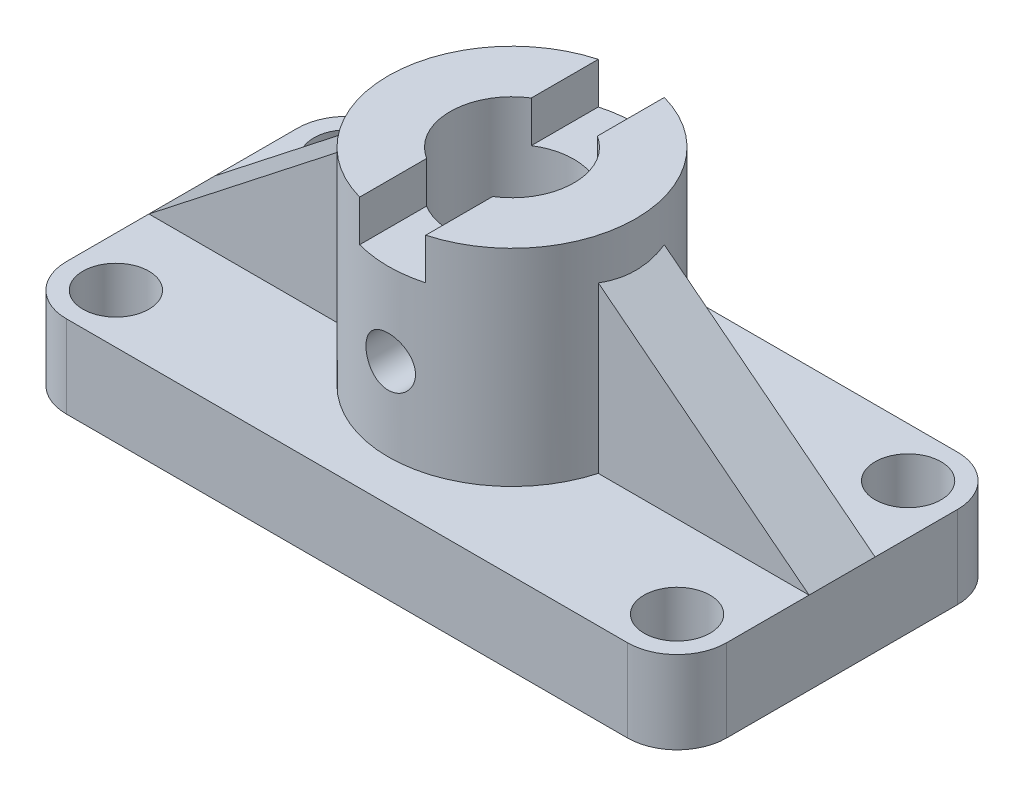
SolidWorks part; units mm, degrees
ref_plane "前视基准面" through (0, 0, 0) normal (0, 0, 1) x (1, 0, 0)
ref_plane "上视基准面" through (0, 0, 0) normal (0, 1, 0) x (1, 0, 0)
ref_plane "右视基准面" through (0, 0, 0) normal (1, 0, 0) x (0, 0, -1)
other "Configuration Table"
sketch "草图2" plane through (0, 0, 0) normal (0, 1, 0) x (1, 0, 0)
  line L0 (-1000, 0) -> (49000, 0) construction
  line L1 (34, -20) -> (-34, -20)
  line L2 (40, -14) -> (40, 14)
  line L3 (34, 20) -> (-34, 20)
  line L4 (-40, -14) -> (-40, 14)
  line L5 (40, -20) -> (-40, 20) construction
  line L6 (40, 20) -> (-40, -20) construction
  line L7 (0, -1000) -> (0, 49000) construction
  line L8 (40, -4) -> (14.4568, -4)
  line L9 (-40, 4) -> (-14.4568, 4)
  line L10 (-40, 4) -> (-40, -4)
  line L11 (-40, -4) -> (-14.4568, -4)
  line L13 (40, 4) -> (14.4568, 4)
  arc A0 (-34, -20) -> (-40, -14) centre (-34, -14) cw
  arc A1 (34, -20) -> (40, -14) centre (34, -14) ccw
  arc A2 (34, 20) -> (40, 14) centre (34, 14) cw
  arc A3 (-34, 20) -> (-40, 14) centre (-34, 14) ccw
  circle A4 centre (34, 14) radius 4
  circle A5 centre (34, -14) radius 4
  circle A6 centre (-34, -14) radius 4
  circle A7 centre (-34, 14) radius 4
  circle A8 centre (0, 0) radius 7.5
  circle A9 centre (0, 0) radius 15
  point P0 (0, 0)
  dimension "D1" = 6
  dimension "D4" = 8
  dimension "D5" = 15
  dimension "D6" = 30
  dimension "D2" = 80
  dimension "D3" = 40
  dimension "D7" = 8
extrude "凸台-拉伸1" add sketch "草图2" along normal blind 10 contours A9 L13 L2 A2 L3 A3 L4 L9 A7 A4 | A9 L8 L2 L13 | A9 L11 L4 A0 L1 A1 L2 L8 A5 A6 | A9 L9 L4 L11 region at (0, 0, 19.1842) region at (27.4096, 0, 0) region at (-27.4096, 0, 0) region at (27.2284, 0, -4.8158)
extrude "凸台-拉伸2" add sketch "草图2<3>" along normal blind 35 contours A9 A8 region at (0, 0, 14.5757)
sketch "草图2<3>" plane through (0, 0, 0) normal (0, 1, 0) x (1, 0, 0) same geometry as "草图2"
extrude "凸台-拉伸3" add sketch "草图2<4>" along normal blind 20 from surface separate body contours A9 L9 L4 L11 | A9 L8 L2 L13 region at (27.4096, 0, 0) region at (-27.4096, 0, 0) starting at face at (0, 10, 15)
sketch "草图2<4>" plane through (0, 0, 0) normal (0, 1, 0) x (1, 0, 0) same geometry as "草图2"
sketch "草图4" plane through (0, 0, 4) normal (0, 0, 1) x (1, 0, 0)
  line L0 (-40, 10) -> (-14.4568, 30)
  line L1 (14.4568, 30) -> (40, 10)
  line L5 (40, 10) -> (40, 30) construction
  line L6 (40, 30) -> (14.4568, 30) construction
  line L10 (-14.4568, 30) -> (-40, 30) construction
  line L11 (-40, 30) -> (-40, 10) construction
  line L13 (40, 10) -> (40, 30)
  line L14 (40, 30) -> (14.4568, 30)
  line L18 (-14.4568, 30) -> (-40, 30)
  line L19 (-40, 30) -> (-40, 10)
extrude "切除-拉伸1" cut sketch "草图4" against normal through all
sketch "草图5" plane through (0, 35, 0) normal (0, 1, 0) x (1, 0, 0)
  line L2 (-4, -14.4568) -> (-4, 14.4568)
  line L4 (4, -14.4568) -> (4, 14.4568)
  circle A0 centre (0, 0) radius 15 construction
  circle A1 centre (0, 0) radius 15 construction
  arc A2 (-4, -14.4568) -> (4, -14.4568) centre (0, 0) ccw
  arc A3 (4, 14.4568) -> (-4, 14.4568) centre (0, 0) ccw
  dimension "D1" = 8
extrude "切除-拉伸2" cut sketch "草图5" against normal blind 5
sketch "草图6" plane through (0, 0, 0) normal (0, 0, 1) x (1, 0, 0)
  line L1 (4, 30) -> (-4, 30) construction
  circle A0 centre (0, 20) radius 3
  dimension "D2" = 6
  dimension "D1" = 10
extrude "切除-拉伸3" cut sketch "草图6" against normal through all both and the other way through all
